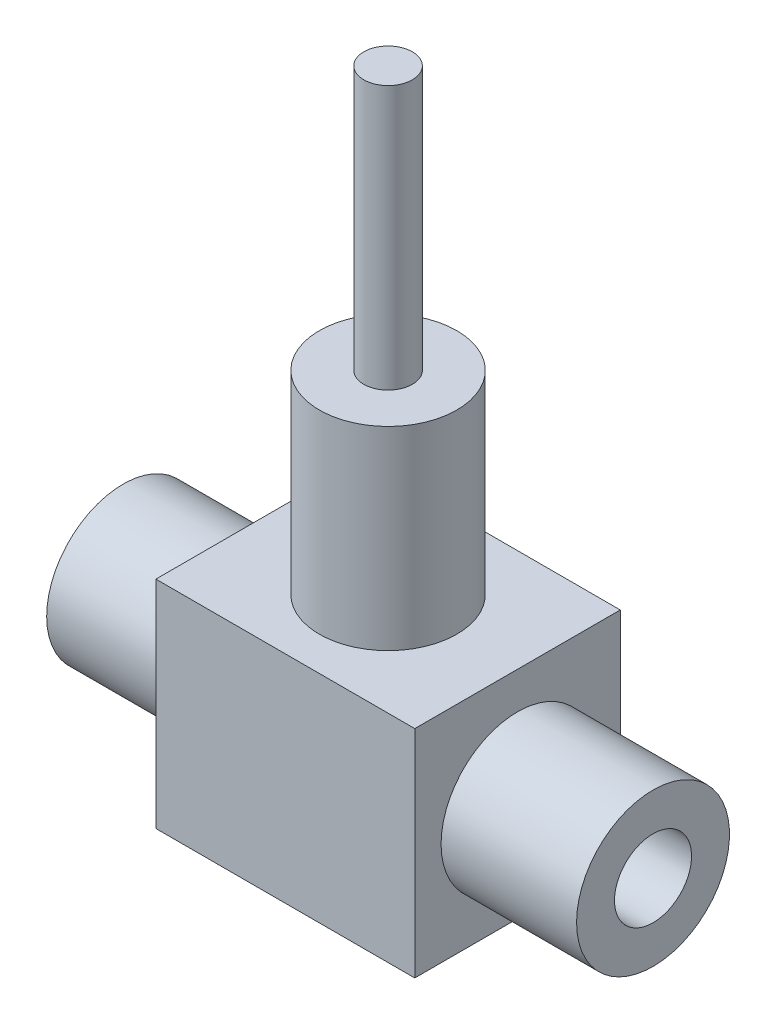
SolidWorks part; units mm, degrees
ref_plane "Front Plane" through (0, 0, 0) normal (0, 0, 1) x (1, 0, 0)
ref_plane "Top Plane" through (0, 0, 0) normal (0, 1, 0) x (1, 0, 0)
ref_plane "Right Plane" through (0, 0, 0) normal (1, 0, 0) x (0, 0, -1)
sketch "Body Sketch" plane through (0, 0, 0) normal (0, 0, 1) x (1, 0, 0)
  line L0 (-16, -12.7) -> (16, -12.7)
  line L1 (16, -12.7) -> (16, 14)
  line L2 (16, 14) -> (-16, 14)
  line L3 (-16, 14) -> (-16, -12.7)
extrude "Body" add sketch "Body Sketch" along normal mid plane 25.4
ref_axis "Engine Axis" through (36.025, 0, 0) along (-1, 0, 0)
ref_axis "Stem Axis" through (0, -16.865, 0) along (0, 1, 0)
sketch "Nut +X Sketch" plane through (0, 0, 0) normal (0, 0, 1) x (1, 0, 0)
  line L0 (-1000, 0) -> (1000, 0) construction
  line L1 (16, 0) -> (32.75, 0)
  line L2 (32.75, 0) -> (32.75, 9.45)
  line L3 (32.75, 9.45) -> (16, 9.45)
  line L4 (16, 9.45) -> (16, 0)
revolve "Nut +X" add sketch "Nut +X Sketch" angle 360 about L0
sketch "Nut -X Sketch" plane through (0, 0, 0) normal (0, 0, 1) x (1, 0, 0)
  line L0 (-1000, 0) -> (1000, 0) construction
  line L1 (-32.75, 0) -> (-16, 0)
  line L2 (-16, 0) -> (-16, 9.45)
  line L3 (-16, 9.45) -> (-32.75, 9.45)
  line L4 (-32.75, 9.45) -> (-32.75, 0)
revolve "Nut -X" add sketch "Nut -X Sketch" angle 360 about L0
sketch "Socket +X Sketch" plane through (0, 0, 0) normal (0, 0, 1) x (1, 0, 0)
  line L0 (-1000, 0) -> (1000, 0) construction
  line L1 (15.95, 0) -> (33.75, 0)
  line L2 (33.75, 0) -> (33.75, 4.7625)
  line L3 (33.75, 4.7625) -> (15.95, 4.7625)
  line L4 (15.95, 4.7625) -> (15.95, 0)
revolve "Socket +X" cut sketch "Socket +X Sketch" angle 360 about L0
sketch "Socket -X Sketch" plane through (0, 0, 0) normal (0, 0, 1) x (1, 0, 0)
  line L0 (-1000, 0) -> (1000, 0) construction
  line L1 (-33.75, 0) -> (-15.95, 0)
  line L2 (-15.95, 0) -> (-15.95, 4.7625)
  line L3 (-15.95, 4.7625) -> (-33.75, 4.7625)
  line L4 (-33.75, 4.7625) -> (-33.75, 0)
revolve "Socket -X" cut sketch "Socket -X Sketch" angle 360 about L0
sketch "Stem Sketch" plane through (0, 0, 0) normal (0, 0, 1) x (1, 0, 0)
  line L0 (0, -500) -> (0, 500) construction
  line L1 (0, 14) -> (8.5, 14)
  line L2 (8.5, 14) -> (8.5, 38)
  line L3 (8.5, 38) -> (3, 38)
  line L4 (3, 38) -> (3, 70.6)
  line L5 (3, 70.6) -> (0, 70.6)
  line L6 (0, 70.6) -> (0, 14)
revolve "Stem" add sketch "Stem Sketch" angle 360 about L0
